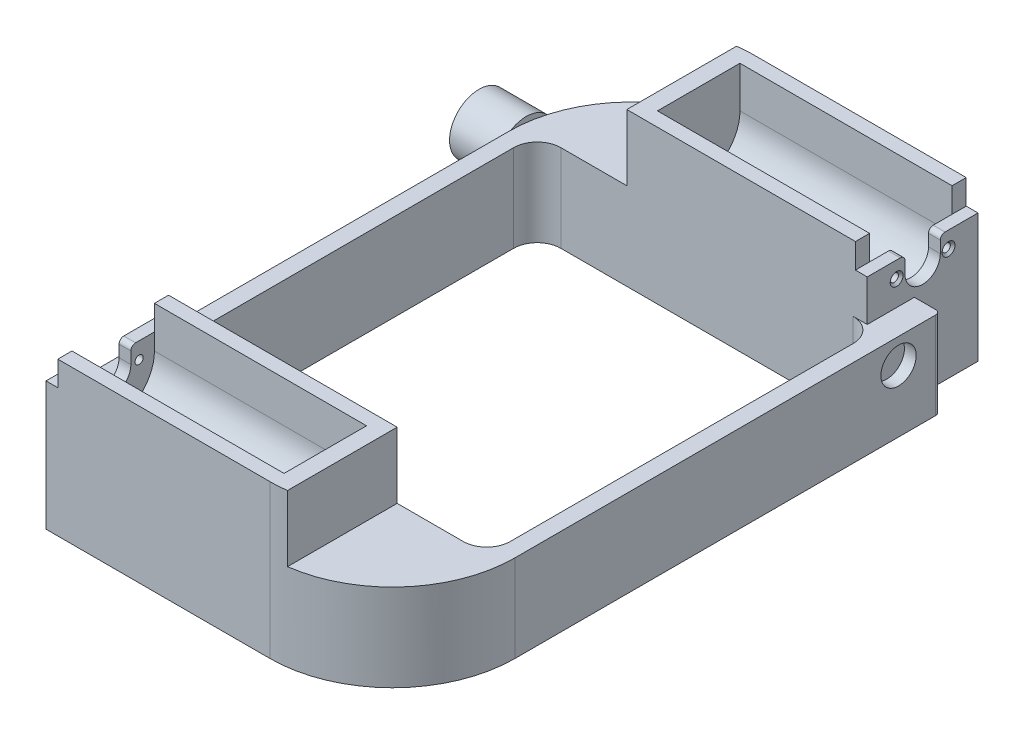
SolidWorks part; units mm, degrees
ref_plane "Front Plane" through (0, 0, 0) normal (0, 0, 1) x (1, 0, 0)
ref_plane "Top Plane" through (0, 0, 0) normal (0, 1, 0) x (1, 0, 0)
ref_plane "Right Plane" through (0, 0, 0) normal (1, 0, 0) x (0, 0, -1)
ref_axis "Center Axis" through (0, 23.7128, 0) along (0, -1, 0)
sketch "Sketch1" plane through (0, 0, 0) normal (1, 0, 0) x (0, 0, -1)
  line L0 (-159.8432, -20) -> (183.538, -20) construction
  line L1 (23.9696, -38.5304) -> (68.7681, 6.2681) construction
  line L2 (44.3566, -9.3934) -> (44.3566, -0.6434)
  line L3 (61.8566, -9.3934) -> (61.8566, -0.6434)
  line L4 (41.3566, -0.6434) -> (41.3566, -33.1434)
  line L5 (41.3566, -33.1434) -> (64.8566, -33.1434)
  line L6 (41.3566, -0.6434) -> (44.3566, -0.6434)
  line L7 (61.8566, -0.6434) -> (64.8566, -0.6434)
  line L8 (64.8566, -33.1434) -> (64.8566, -0.6434)
  arc A0 (44.3566, -9.3934) -> (61.8566, -9.3934) centre (53.1066, -9.3934) ccw
  point P1 (42.5, -20)
  point P13 (0, 0)
  dimension "D1" = 20
  dimension "D4" = 8.75
  dimension "D2" = 42.5
  dimension "D3" = 45
  dimension "D5" = 8.75
  dimension "D6" = 15
  dimension "D7" = 32.5
  dimension "D8" = 3
  dimension "D9" = 3
extrude "FrontMotorBracket" add sketch "Sketch1" along normal blind 45 from offset 13.5 offset against normal yes
sketch "Sketch8" plane through (0, 0, 0) normal (1, 0, 0) x (0, 0, -1)
  line L0 (-79.9426, -20) -> (109.5131, -20) construction
  line L1 (-68.835, 6.335) -> (-18.9148, -43.5852) construction
  line L2 (-61.8566, -9.3934) -> (-61.8566, -0.6434)
  line L3 (-64.8566, -0.6434) -> (-64.8566, -33.1434)
  line L4 (-44.3566, -0.6434) -> (-44.3566, -9.3934)
  line L5 (-64.8566, -33.1434) -> (-41.3566, -33.1434)
  line L6 (-64.8566, -0.6434) -> (-61.8566, -0.6434)
  line L7 (-44.3566, -0.6434) -> (-41.3566, -0.6434)
  line L8 (-41.3566, -33.1434) -> (-41.3566, -0.6434)
  arc A0 (-61.8566, -9.3934) -> (-44.3566, -9.3934) centre (-53.1066, -9.3934) ccw
  point P5 (-42.5, -20)
  dimension "D5" = 8.75
  dimension "D1" = 20
  dimension "D2" = 42.5
  dimension "D3" = 45
  dimension "D4" = 15
  dimension "D6" = 8.75
  dimension "D7" = 3
  dimension "D8" = 3
  dimension "D9" = 32.5
extrude "RearMotorBracket" add sketch "Sketch8" against normal blind 45 from offset 13.5 separate body
sketch "Sketch5" plane through (31.5, 0, 0) normal (1, 0, 0) x (0, 0, -1)
  line L0 (49.3566, -6.8934) -> (49.3566, -9.3934)
  line L1 (41.3566, -5.8934) -> (41.3566, -33.1434)
  line L2 (41.3566, -33.1434) -> (64.8566, -33.1434)
  line L3 (41.3566, -5.8934) -> (48.3566, -5.8934)
  line L5 (56.8566, -6.8934) -> (56.8566, -9.3934)
  line L6 (57.8566, -5.8934) -> (64.8566, -5.8934)
  line L8 (64.8566, -33.1434) -> (64.8566, -5.8934)
  arc A3 (48.3566, -5.8934) -> (49.3566, -6.8934) centre (48.3566, -6.8934) cw
  arc A4 (49.3566, -9.3934) -> (56.8566, -9.3934) centre (53.1066, -9.3934) ccw
  arc A5 (49.3566, -9.3934) -> (56.8566, -9.3934) centre (53.1066, -9.3934) ccw
  arc A6 (57.8566, -5.8934) -> (56.8566, -6.8934) centre (57.8566, -6.8934) ccw
  dimension "D3" = 1
  dimension "D4" = 1
  dimension "D2" = 3.5
  dimension "D1" = 5
extrude "FrontMotorPlate" add sketch "Sketch5" along normal blind 2.5
sketch "Sketch9" plane through (-31.5, 0, 0) normal (-1, 0, 0) x (0, 0, 1)
  line L0 (41.3566, -5.8934) -> (41.3566, -33.1434)
  line L2 (41.3566, -5.8934) -> (48.3566, -5.8934)
  line L3 (49.3566, -6.8934) -> (49.3566, -9.3934)
  line L4 (56.8566, -9.3934) -> (56.8566, -6.8934)
  line L5 (57.8566, -5.8934) -> (64.8566, -5.8934)
  line L7 (41.3566, -33.1434) -> (64.8566, -33.1434)
  line L8 (64.8566, -33.1434) -> (64.8566, -5.8934)
  arc A4 (48.3566, -5.8934) -> (49.3566, -6.8934) centre (48.3566, -6.8934) cw
  arc A5 (49.3566, -9.3934) -> (56.8566, -9.3934) centre (53.1066, -9.3934) ccw
  arc A6 (49.3566, -9.3934) -> (56.8566, -9.3934) centre (53.1066, -9.3934) ccw
  arc A7 (56.8566, -6.8934) -> (57.8566, -5.8934) centre (57.8566, -6.8934) cw
  dimension "D3" = 1
  dimension "D4" = 1
  dimension "D2" = 3.5
  dimension "D1" = 5
extrude "RearMotorPlate" add sketch "Sketch9" along normal blind 2.5
sketch "Sketch6" plane through (34, 0, 0) normal (1, 0, 0) x (0, 0, -1)
  line L0 (35.2696, -9.3934) -> (72.8501, -9.3934) construction
  line L1 (53.1066, 12.6171) -> (53.1066, -36.011) construction
  arc A0 (49.3566, -9.3934) -> (56.8566, -9.3934) centre (53.1066, -9.3934) ccw construction
  arc A1 (49.3566, -9.3934) -> (56.8566, -9.3934) centre (53.1066, -9.3934) ccw construction
  circle A2 centre (47.6066, -9.3934) radius 0.875
  circle A3 centre (58.6066, -9.3934) radius 0.875
  dimension "D2" = 1.75
  dimension "D1" = 11
extrude "FrontMotorScrewHoles" cut sketch "Sketch6" against normal up to next (2.5 mm away)
sketch "Sketch10" plane through (-34, 0, 0) normal (-1, 0, 0) x (0, 0, 1)
  line L0 (33.7961, -9.3934) -> (79.1637, -9.3934) construction
  line L1 (53.1066, 11.6109) -> (53.1066, -30.6773) construction
  arc A0 (49.3566, -9.3934) -> (56.8566, -9.3934) centre (53.1066, -9.3934) ccw construction
  arc A1 (49.3566, -9.3934) -> (56.8566, -9.3934) centre (53.1066, -9.3934) ccw construction
  circle A2 centre (47.6066, -9.3934) radius 0.875
  circle A3 centre (58.6066, -9.3934) radius 0.875
  dimension "D1" = 1.75
  dimension "D2" = 11
extrude "RearMotorScrewHoles" cut sketch "Sketch10" against normal up to next (2.5 mm away)
chamfer "FrontMotorScrewChamfer" distance 0.5 angle 45 2 edges at (34, -9.3934, -59.4816) (34, -9.3934, -48.4816)
chamfer "RearMotorScrewChamfer" distance 0.5 angle 45 2 edges at (-34, -9.3934, 59.4816) (-34, -9.3934, 48.4816)
sketch "Sketch12" plane through (0, -33.1434, 0) normal (0, -1, 0) x (-1, 0, 0)
  line L0 (-34, 41.3566) -> (13.5, 41.3566) construction
  line L1 (-36, 36.3566) -> (-36, -36.3566)
  line L2 (-34, 51.3566) -> (-38.5, 51.3566)
  line L3 (13.5, 64.8566) -> (13.5, 41.3566)
  line L4 (-13.5, -41.3566) -> (-31, -41.3566)
  line L5 (-39.5, 50.3566) -> (-39.5, -38.8566)
  line L6 (13.5, 41.3566) -> (31, 41.3566)
  line L7 (-34, 41.3566) -> (-34, 64.8566) construction
  line L8 (-34, 51.3566) -> (-34, 41.3566)
  line L9 (-34, 41.3566) -> (-31, 41.3566)
  line L10 (34, -64.8566) -> (-13.5, -64.8566) construction
  line L11 (-13.5, -64.8566) -> (-13.5, -41.3566) construction
  line L12 (-13.5, -64.8566) -> (-13.5, -41.3566)
  line L13 (36, -36.3566) -> (36, 36.3566)
  line L14 (-165.3195, 0) -> (124.3922, 0) construction
  line L15 (39.5, -50.3566) -> (39.5, 38.8566)
  line L16 (34, -41.3566) -> (31, -41.3566)
  line L17 (34, -51.3566) -> (34, -41.3566)
  line L18 (34, -51.3566) -> (38.5, -51.3566)
  arc A0 (-31, 41.3566) -> (-36, 36.3566) centre (-31, 36.3566) ccw
  arc A1 (-31, -41.3566) -> (-36, -36.3566) centre (-31, -36.3566) cw
  arc A2 (-38.5, 51.3566) -> (-39.5, 50.3566) centre (-38.5, 50.3566) ccw
  arc A3 (-39.5, -38.8566) -> (-13.5, -64.8566) centre (-13.5, -38.8566) ccw
  arc A4 (39.5, 38.8566) -> (13.5, 64.8566) centre (13.5, 38.8566) ccw
  arc A5 (31, 41.3566) -> (36, 36.3566) centre (31, 36.3566) cw
  arc A6 (31, -41.3566) -> (36, -36.3566) centre (31, -36.3566) ccw
  arc A7 (38.5, -51.3566) -> (39.5, -50.3566) centre (38.5, -50.3566) ccw
  point P47 (0, 0)
  dimension "D2" = 5
  dimension "D3" = 5
  dimension "D4" = 1
  dimension "D1" = 17.5
  dimension "D5" = 4.5
  dimension "D6" = 10
  dimension "D7" = 2
extrude "FrameExtrude" add sketch "Sketch12" against normal blind 18.5
sketch "Sketch13" plane through (39.5, 0, 0) normal (1, 0, 0) x (0, 0, -1)
  line L0 (53.1066, -9.3934) -> (43.0852, -19.4148) construction
  line L1 (0, 0) -> (81.1646, 0) construction
  circle A0 centre (42.5, -20) radius 3.75
  arc A1 (49.3566, -9.3934) -> (56.8566, -9.3934) centre (53.1066, -9.3934) ccw construction
  arc A2 (49.3566, -9.3934) -> (56.8566, -9.3934) centre (53.1066, -9.3934) ccw construction
  dimension "D3" = 7.5
  dimension "D1" = 45
  dimension "D2" = 15
extrude "BearingCutRight" cut sketch "Sketch13" against normal blind 2.5
sketch "Sketch14" plane through (-39.5, 0, 0) normal (-1, 0, 0) x (0, 0, 1)
  line L0 (68.458, 5.958) -> (26.864, -35.636) construction
  circle A0 centre (42.5, -20) radius 3.75
  arc A2 (49.3566, -9.3934) -> (56.8566, -9.3934) centre (53.1066, -9.3934) ccw construction
  arc A3 (49.3566, -9.3934) -> (56.8566, -9.3934) centre (53.1066, -9.3934) ccw construction
  dimension "D2" = 7.5
  dimension "D4" = 15
extrude "BearingCutLeft" cut sketch "Sketch14" against normal blind 2.5
sketch "Sketch15" plane through (0, -14.6434, 0) normal (0, 1, 0) x (1, 0, 0)
  line L0 (-13.5, 41.3566) -> (-17, 41.3566)
  line L1 (-13.5, 41.3566) -> (-31, 41.3566) construction
  line L2 (-17, 41.3566) -> (-17, 64.6199)
  line L4 (-13.5, 64.8566) -> (-13.5, 41.3566)
  line L5 (17, -41.3566) -> (17, -64.6199)
  line L6 (13.5, -41.3566) -> (31, -41.3566) construction
  line L7 (17, -41.3566) -> (13.5, -41.3566)
  line L8 (13.5, -41.3566) -> (13.5, -64.8566)
  arc A0 (-13.5, 64.8566) -> (-39.5, 38.8566) centre (-13.5, 38.8566) ccw construction
  arc A1 (-13.5, 64.8566) -> (-17, 64.6199) centre (-13.5, 38.8566) ccw
  arc A2 (13.5, -64.8566) -> (39.5, -38.8566) centre (13.5, -38.8566) ccw construction
  arc A3 (13.5, -64.8566) -> (17, -64.6199) centre (13.5, -38.8566) ccw
  dimension "D1" = 3.5
  dimension "D2" = 3.5
extrude "MotorEnclosureRearExtrude" add sketch "Sketch15" along normal up to surface (14 mm away) up to face at (9, -0.6434, -63.3566)
sketch "Sketch16" plane through (-39.5, 0, 0) normal (-1, 0, 0) x (0, 0, 1)
  circle A0 centre (-42.5, -20) radius 6.25
  circle A2 centre (42.5, -20) radius 3.75 construction
  circle A3 centre (42.5, -20) radius 3.75 construction
  dimension "D1" = 12.5
  dimension "D2" = 85
extrude "Boss-Extrude3" add sketch "Sketch16" along normal blind 10
sketch "Sketch17" plane through (-49.5, 0, 0) normal (-1, 0, 0) x (0, 0, 1)
  circle A0 centre (-42.5, -20) radius 4.25
  circle A1 centre (-42.5, -20) radius 6.25 construction
  dimension "D1" = 8.5
extrude "Cut-Extrude3" cut sketch "Sketch17" against normal blind 2.5
